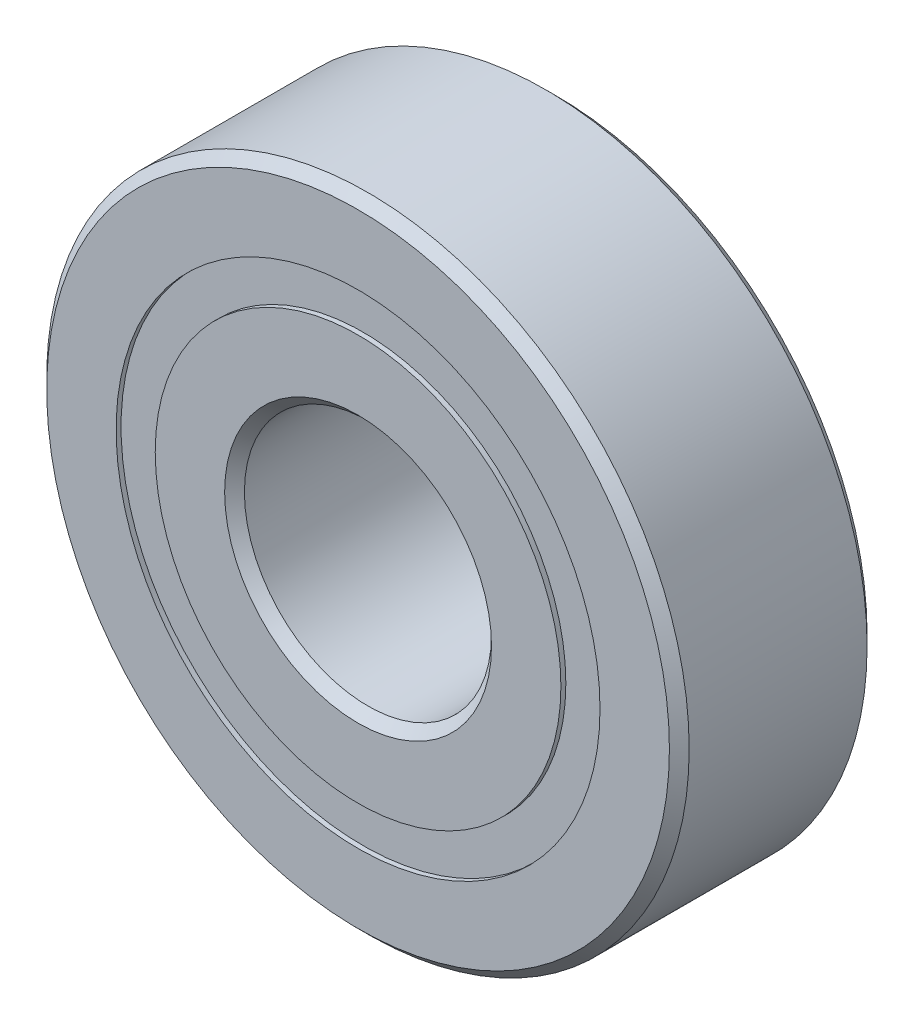
SolidWorks part; units mm, degrees
ref_plane "Front Plane" through (0, 0, 0) normal (0, 0, 1) x (1, 0, 0)
ref_plane "Top Plane" through (0, 0, 0) normal (0, 1, 0) x (1, 0, 0)
ref_plane "Right Plane" through (0, 0, 0) normal (1, 0, 0) x (0, 0, -1)
sketch "Sketch1" plane through (0, 0, 0) normal (1, 0, 0) x (0, 0, -1)
  line L0 (-2, 0) -> (2, 0) construction
  line L1 (0, 6.5) -> (0, -6.5) construction
  line L2 (1.8, 6.5) -> (-1.8, 6.5)
  line L3 (-1.8, 6.5) -> (-2, 6.3)
  line L4 (-2, 6.3) -> (-2, 4.8956)
  line L5 (-2, 4.8956) -> (-0.8889, 4.8956)
  line L6 (2, 4.8956) -> (0.8889, 4.8956)
  line L7 (2, 6.3) -> (2, 4.8956)
  line L8 (1.8, 6.5) -> (2, 6.3)
  line L9 (0, 6.5) -> (0, 4.5) construction
  line L10 (0, 4.5) -> (0, 2.5) construction
  arc A0 (-0.8889, 4.8956) -> (0.8889, 4.8956) centre (0, 4.5) cw
  point P14 (0, 2.5)
  dimension "Width" = 4
  dimension "OD" = 13
  dimension "D1" = 45
  dimension "D2" = 0.2
  dimension "Shaft Dia" = 5
  dimension "D3" = 1.7778
  dimension "D4" = 0.3956
revolve "Revolve1" add sketch "Sketch1" angle 360 about L0
sketch "Sketch3" plane through (0, 0, 0) normal (1, 0, 0) x (0, 0, -1)
  line L0 (-2, 4.1044) -> (-0.8889, 4.1044)
  line L1 (0, 6.5) -> (0, -6.5) construction
  line L2 (-2, 6.3) -> (-2, 4.8956) construction
  line L3 (-2, 4.1044) -> (-2, 2.7)
  line L4 (-1.8, 6.5) -> (-2, 6.3) construction
  line L5 (-2, 2.7) -> (-1.8, 2.5)
  line L6 (-1.8, 2.5) -> (1.8, 2.5)
  line L7 (1.8, 6.5) -> (1.8, -6.5) construction
  line L8 (1.8, 2.5) -> (2, 2.7)
  line L9 (2, -6.3) -> (2, 6.3) construction
  line L10 (2, 2.7) -> (2, 4.1044)
  line L11 (2, 4.1044) -> (0.8889, 4.1044)
  line L13 (1.8, 6.5) -> (2, 6.3) construction
  arc A0 (0.8889, 4.8956) -> (-0.8889, 4.8956) centre (0, 4.5) ccw construction
  arc A1 (0.8889, 4.1044) -> (-0.8889, 4.1044) centre (0, 4.5) cw
revolve "Revolve3" add sketch "Sketch3" angle 360 about L0
sketch "Sketch4" plane through (0, 0, 0) normal (1, 0, 0) x (0, 0, -1)
  line L0 (-0.9729, 4.5) -> (0.9729, 4.5)
  arc A2 (-0.9729, 4.5) -> (0.9729, 4.5) centre (0, 4.5) cw
  arc A3 (0.8889, 4.8956) -> (-0.8889, 4.8956) centre (0, 4.5) ccw construction
revolve "Revolve4" add sketch "Sketch4" angle 360 about L0
ref_axis "Axis1" through (0, 0, -2) along (0, 0, 1)
pattern_circular "CirPattern1" count 12 every 30 about axis through (0, 0, -2) along (0, 0, 1) of bodies 104
sketch "Sketch5" plane through (0, 0, 0) normal (1, 0, 0) x (0, 0, -1)
  line L0 (-2, 4.8956) -> (-0.8889, 4.8956) construction
  line L1 (-1.9, 4.8956) -> (-0.9729, 4.8956)
  line L2 (-1.9, 4.8956) -> (-1.9, 4.1044)
  line L3 (-1.9, 4.1044) -> (-0.9729, 4.1044)
  line L4 (-0.9729, 4.8956) -> (-0.9729, 4.1044)
  line L5 (-2, 4.1044) -> (-0.8889, 4.1044) construction
  line L6 (2, 4.8956) -> (0.8889, 4.8956) construction
  line L7 (1.9, 4.8956) -> (0.9729, 4.8956)
  line L8 (1.9, 4.8956) -> (1.9, 4.1044)
  line L9 (1.9, 4.1044) -> (0.9729, 4.1044)
  line L10 (0.9729, 4.8956) -> (0.9729, 4.1044)
  line L11 (2, 4.1044) -> (0.8889, 4.1044) construction
  line L12 (-1.8, 6.5) -> (-2, 6.3) construction
  point P18 (-1.9, 6.4)
revolve "Revolve5" add sketch "Sketch5" angle 360 about L0
sketch "Sketch6" plane through (0, 0, 0) normal (1, 0, 0) x (0, 0, -1)
  line L0 (2, 0) -> (-2, 0) construction
  line L1 (2, 4.8956) -> (0.9, 4.8956)
  line L2 (2, 4.8956) -> (2, 9.5)
  line L3 (2, 9.5) -> (0.9, 9.5)
  line L4 (0.9, 4.8956) -> (0.9, 9.5)
  dimension "Th" = 1.1
  dimension "Flange OD" = 19
revolve "Revolve6" [suppressed] add sketch "Sketch6" angle 360 about L0
equation "\"D2@Sketch1\" = \"Width@Sketch1\"*.05"
equation "\"D3@Sketch1\" = \"Width@Sketch1\"/2.25"
equation "\"D4@Sketch1\" = (((\"OD@Sketch1\"-\"Width@Sketch1\")/2)/3.25)/3.5"
equation "\"D2@CirPattern1\" = 360/\"Balls@CirPattern1\""
